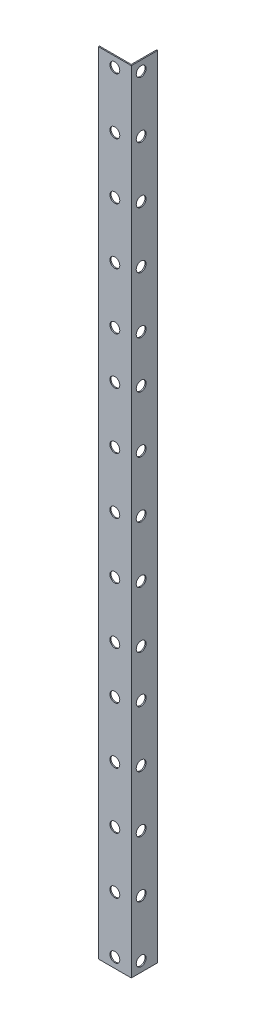
SolidWorks part; units mm, degrees
material "6061-T6 (SS)"
ref_plane "Alzado" through (0, 0, 0) normal (0, 0, 1) x (1, 0, 0)
ref_plane "Planta" through (0, 0, 0) normal (0, 1, 0) x (1, 0, 0)
ref_plane "Vista lateral" through (0, 0, 0) normal (1, 0, 0) x (0, 0, -1)
sketch "Sketch1" plane through (0, 0, 0) normal (0, 1, 0) x (1, 0, 0)
  line L0 (0, 0) -> (15, 0)
  line L1 (15, 0) -> (15, 12)
  line L2 (15, 12) -> (14.5, 12)
  line L3 (14.5, 12) -> (14.5, 0.5)
  line L4 (14.5, 0.5) -> (0, 0.5)
  line L5 (0, 0.5) -> (0, 0)
  dimension "D1" = 15
  dimension "D2" = 12
  dimension "D3" = 0.5
  dimension "D4" = 0.5
extrude "Boss-Extrude1" add sketch "Sketch1" along normal blind 360
sketch "Sketch2" plane through (14.5, 0, 0) normal (-1, 0, 0) x (0, 0, 1)
  circle A0 centre (-4.5, 355.5) radius 2.25
  circle A1 centre (-4.5, 329.8125) radius 2.25
  circle A2 centre (-4.5, 304.125) radius 2.25
  circle A3 centre (-4.5, 278.4375) radius 2.25
  circle A4 centre (-4.5, 252.75) radius 2.25
  circle A5 centre (-4.5, 231.375) radius 2.25
  circle A6 centre (-4.5, 205.6875) radius 2.25
  circle A7 centre (-4.5, 180) radius 2.25
  circle A8 centre (-4.5, 154.3125) radius 2.25
  circle A9 centre (-4.5, 128.625) radius 2.25
  circle A10 centre (-4.5, 107.25) radius 2.25
  circle A11 centre (-4.5, 81.5625) radius 2.25
  circle A12 centre (-4.5, 55.875) radius 2.25
  circle A13 centre (-4.5, 30.1875) radius 2.25
  circle A14 centre (-4.5, 4.5) radius 2.25
  point P45 (0, 0)
  point P46 (-4.5, 355.5)
  dimension "D1" = 4.5
extrude "Cut-Extrude1" cut sketch "Sketch2" against normal up to next
sketch "Sketch3" plane through (0, 0, 0) normal (0, 0, 1) x (1, 0, 0)
  circle A0 centre (7.5, 355.5) radius 2.25
  circle A1 centre (7.5, 329.8437) radius 2.25
  circle A2 centre (7.5, 304.1875) radius 2.25
  circle A3 centre (7.5, 278.5312) radius 2.25
  circle A4 centre (7.5, 252.875) radius 2.25
  circle A5 centre (7.5, 231.3125) radius 2.25
  circle A6 centre (7.5, 205.6562) radius 2.25
  circle A7 centre (7.5, 180) radius 2.25
  circle A8 centre (7.5, 154.3437) radius 2.25
  circle A9 centre (7.5, 128.6875) radius 2.25
  circle A10 centre (7.5, 107.125) radius 2.25
  circle A11 centre (7.5, 81.4687) radius 2.25
  circle A12 centre (7.5, 55.8125) radius 2.25
  circle A13 centre (7.5, 30.1562) radius 2.25
  circle A14 centre (7.5, 4.5) radius 2.25
  dimension "D1" = 4.5
extrude "Cut-Extrude2" cut sketch "Sketch3" against normal up to next
